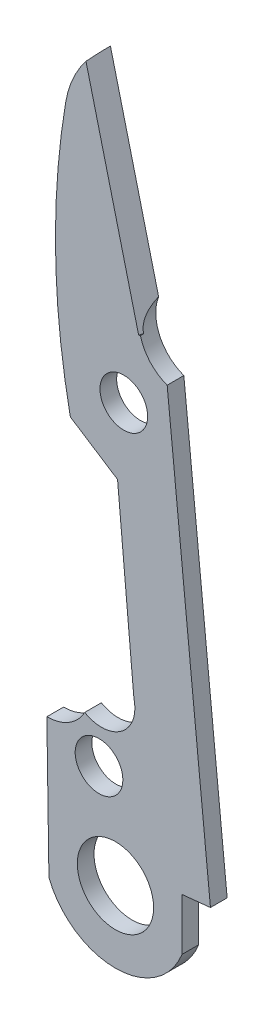
SolidWorks part; units mm, degrees
material "AISI 4340 Steel, normalized"
ref_plane "Front Plane" through (0, 0, 0) normal (0, 0, 1) x (1, 0, 0)
ref_plane "Top Plane" through (0, 0, 0) normal (0, 1, 0) x (1, 0, 0)
ref_plane "Right Plane" through (0, 0, 0) normal (1, 0, 0) x (0, 0, -1)
sketch "Sketch1" plane through (0, 0, 0) normal (0, 0, 1) x (1, 0, 0)
  line L0 (16.7881, 37.7732) -> (83.9405, 37.7732) construction
  line L1 (53.9966, 56.543) -> (56.5636, 46.2645)
  line L2 (57.9078, 43.2984) -> (60.2136, 20.3565)
  line L3 (60.2136, 20.3565) -> (58.6972, 20.2041)
  line L4 (58.6972, 20.2041) -> (58.6972, 17.4355)
  line L5 (51.5002, 24.8015) -> (51.6106, 17.4355)
  line L6 (52.752, 39.2541) -> (55.2654, 37.6285)
  line L7 (55.2654, 37.6285) -> (56.1361, 27.9754)
  arc A0 (52.4996, 53.6305) -> (52.752, 39.2541) centre (91.2768, 47.121) ccw
  arc A1 (52.4996, 53.6305) -> (53.9966, 56.543) centre (57.8183, 52.7376) cw
  arc A2 (56.5636, 46.2645) -> (57.9078, 43.2984) centre (58.6972, 45.4438) ccw
  arc A3 (51.6106, 17.4355) -> (58.6972, 17.4355) centre (55.1539, 18.8359) ccw
  arc A4 (56.1361, 27.9754) -> (53.5156, 26.0086) centre (54.411, 27.5447) cw
  arc A5 (53.5156, 26.0086) -> (51.5002, 24.8015) centre (51.5002, 27.0875) cw
  circle A6 centre (55.5984, 41.3369) radius 1.27
  circle A7 centre (54.2776, 23.9125) radius 1.27
  point P21 (0, 0)
  point P26 (0, 0)
  point P27 (0, 0)
  point P28 (0, 0)
  point P29 (0, 0)
  point P30 (0, 0)
  point P31 (0, 0)
  point P32 (0, 0)
  point P33 (0, 0)
  point P35 (49.8236, 43.5859)
  point P36 (54.3879, 41.7258)
  dimension "D1" = 2.54
  dimension "D3" = 3.81
  dimension "D7" = 5.3932
  dimension "D8" = 39.3197
  dimension "D12" = 2.286
  dimension "D13" = 1.778
  dimension "D29" = 2.286
  dimension "D30" = 17.4244
  dimension "D31" = 1.3208
  dimension "D2" = 8.6458
  dimension "D4" = 1.524
  dimension "D5" = 36.6268
  dimension "D6" = 0.585
  dimension "D9" = 2.9933
  dimension "D10" = 9.6531
  dimension "D11" = 7.366
  dimension "D14" = 6.477
  dimension "D15" = 2.667
  dimension "D16" = 4.4196
  dimension "D17" = 6.477
  dimension "D18" = 3.7084
  dimension "D19" = 3.556
  dimension "D20" = 3.175
  dimension "D21" = 3.6322
  dimension "D22" = 0.762
  dimension "D23" = 13.716
  dimension "D24" = 15.3416
  dimension "D25" = 29.718
  dimension "D26" = 1.778
  dimension "D27" = 22.352
  dimension "D28" = 2.286
extrude "Boss-Extrude3" add sketch "Sketch1" along normal blind 0.889
sketch "Sketch3" plane through (0, 0, 0.889) normal (0, 0, 1) x (1, 0, 0)
  circle A0 centre (55.1539, 18.8359) radius 2.032
  dimension "D1" = 4.064
extrude "Cut-Extrude1" cut sketch "Sketch3" against normal through all
ref_plane "Plane2" through (-10.3099, 41.282, 0) normal (-0.2423, 0.9702, 0) x (0.9702, 0.2423, 0)
sketch "Sketch4" plane through (-10.3099, 41.282, 0) normal (-0.2423, 0.9702, 0) x (0.9702, 0.2423, 0)
  line L5 (66.088, 0) -> (66.088, -0.889)
  line L7 (63.9299, -0.889) -> (66.088, -0.889) construction
  line L8 (65.5747, -0.889) -> (66.088, -0.889)
  line L9 (65.5747, -0.889) -> (66.088, 0)
  dimension "D1" = 30
extrude "Cut-Extrude2" cut sketch "Sketch4" against normal blind 12.7
